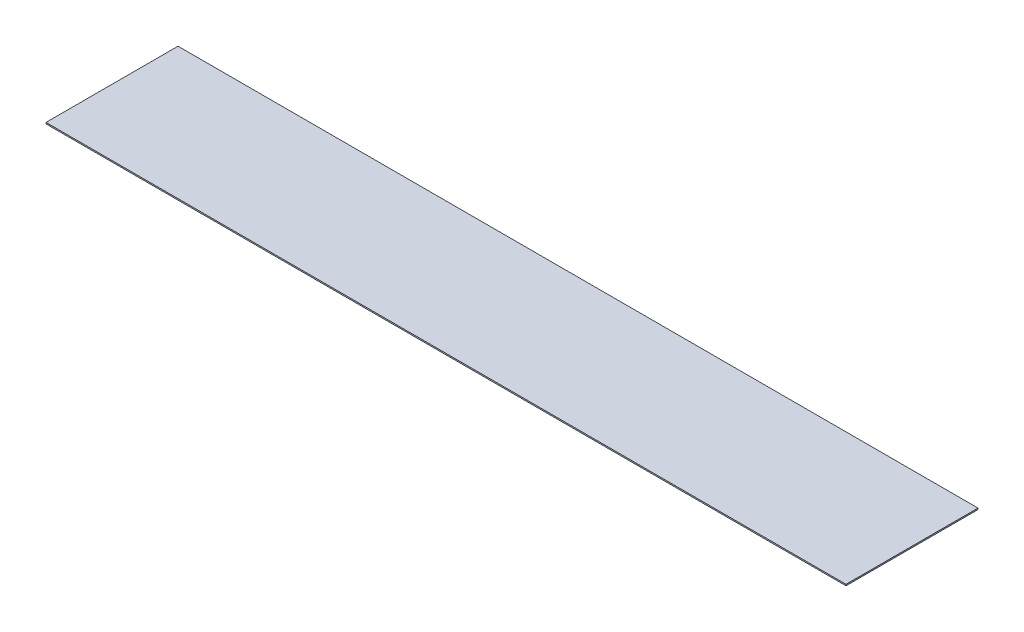
SolidWorks part; units mm, degrees
note: The reader was unsure of these and kept them because the rebuilt part matched: thickness of "Base-Flange1", "Sheet-Metal1".
material "AISI 304"
ref_plane "Front Plane" through (0, 0, 0) normal (0, 0, 1) x (1, 0, 0)
ref_plane "Top Plane" through (0, 0, 0) normal (0, 1, 0) x (1, 0, 0)
ref_plane "Right Plane" through (0, 0, 0) normal (1, 0, 0) x (0, 0, -1)
sketch "Sketch1" plane through (0, 0, 0) normal (0, 1, 0) x (1, 0, 0)
  line L1 (600, -99) -> (-600, -99)
  line L2 (600, -99) -> (600, 99)
  line L3 (600, 99) -> (-600, 99)
  line L4 (-600, -99) -> (-600, 99)
  line L5 (600, -99) -> (-600, 99) construction
  line L6 (600, 99) -> (-600, -99) construction
  point P0 (0, 0)
  dimension "D1" = 1200
  dimension "D2" = 198
base flange "Base-Flange1" sketch "Sketch1" thickness 2 reverse thickness direction no parameters "D1"=0.7366
sketch "Bend-Lines1" [suppressed] plane through (0, 0, 0) normal (0, 1, 0) x (1, 0, 0)
sketch "Bounding-Box1" [suppressed] plane through (0, 0, 0) normal (0, 1, 0) x (1, 0, 0)
sheet metal parameters "Sheet-Metal1" thickness 2 parameters "D1"=0.7366
flat pattern "Flat-Pattern1" [suppressed]
sketch "Bend-Lines2" plane through (0, 0, 0) normal (0, 1, 0) x (1, 0, 0)
sketch3d "Bounding-Box2" [suppressed]
  line L0 (600, -99, 0) -> (-600, -99, 0) construction
  line L1 (600, 99, 0) -> (-600, 99, 0) construction
  line L2 (600, -99, 0) -> (600, 99, 0) construction
  line L3 (-600, -99, 0) -> (-600, 99, 0) construction
equation "\"thickness 1\" = 2"
equation "\"thickness radius 1\"= 3.7366"
equation "\"thickness 2\"= 3"
equation "\"connecting flange\"= 35"
equation "\"main length\"= 1200"
equation "\"main width\"= 1200"
equation "\"divider panel distance offset\"= 296"
equation "\"top panel slot length\"= 250"
equation "\"top panel slot width\"= 700"
equation "\"side panel length\"= 1200"
equation "\"side panel width\"= 950"
equation "\"access hatch length\" = \"access hatch cutout length\" + \"access hatch offset\" * 2"
equation "\"access hatch width\" = \"access hatch cutout width\" + \"access hatch offset\" * 2"
equation "\"access hatch offset X\"= 100"
equation "\"access hatch offset Y\"= 100"
equation "\"back panel access hatch length\"= 1150"
equation "\"back panel access hatch width\"= 206"
equation "\"back panel access hatch flange\"= 40"
equation "\"slotted panel length\" = \"main length\" + 100"
equation "\"slotted panel width\" = \"main width\""
equation "\"slot count x\"= 4"
equation "\"slot count y\"= 9"
equation "\"slot offset\" = \"water tray depth\""
equation "\"slot length\"= 30"
equation "\"slot width\"= 200"
equation "\"slot offset x\" = \"slot length\" + \"slot offset\""
equation "\"slot offset y\" = \"slot width\" + \"slot offset\""
equation "\"drift eliminator size offset\"= 5"
equation "\"drift eliminator length\"= \"back panel access hatch length\" - \"drift eliminator size offset\""
equation "\"drift eliminator width\"= \"back panel access hatch width\" - \"drift eliminator size offset\""
equation "\"drift eliminator depth\" = \"divider panel distance offset\""
equation "\"guide rail flange\"= 40"
equation "\"guid rail flange mount side\"= 20"
equation "\"guid rail back length\" = \"main width\" - \"guide rail flange\" * 2"
equation "\"splash plate length\"= 400"
equation "\"splash plate width\" = \"main width\""
equation "\"splash plate air gap\"= 200"
equation "\"splash plate slot count\"= 11"
equation "\"splash plate slot length\"= 50"
equation "\"splash plate slot height\"= 50"
equation "\"splash plate slot offset\"= 65"
equation "\"water tray depth\"= 150"
equation "\"water tray width\"= 200"
equation "\"water tray panel length\"= 473"
equation "\"dimpled panel length\" = \"main length\" - 200 - \"water tray depth\"/2"
equation "\"dimpled panel top offset\" = \"water tray depth\"/2"
equation "\"dimpled panel width\" = \"main width\""
equation "\"dimple panel slot count\"= 36"
equation "\"dimple panel slot length\"= 8"
equation "\"dimple panel slot width\"= 8"
equation "\"dimple panel slot offset\"= 25"
equation "\"sump base flat section width\"= 300"
equation "\"sump upper depth\"= 300"
equation "\"sump depth\"= 550"
equation "\"leg length\" = \"sump depth\" + 150"
equation "\"leg width\"= 80"
equation "\"leg depth\"= 40"
equation "\"leg support plate size\" = \"leg width\" - \"thickness 2\" * 2"
equation "\"leg base plate thickness\"= 8"
equation "\"D1@Sketch1\"=\"main width\""
equation "\"D2@Sketch1\"=\"water tray width\" - \"thickness 1\""
equation "\"D7@Sheet-Metal1\"=\"thickness 1\""
